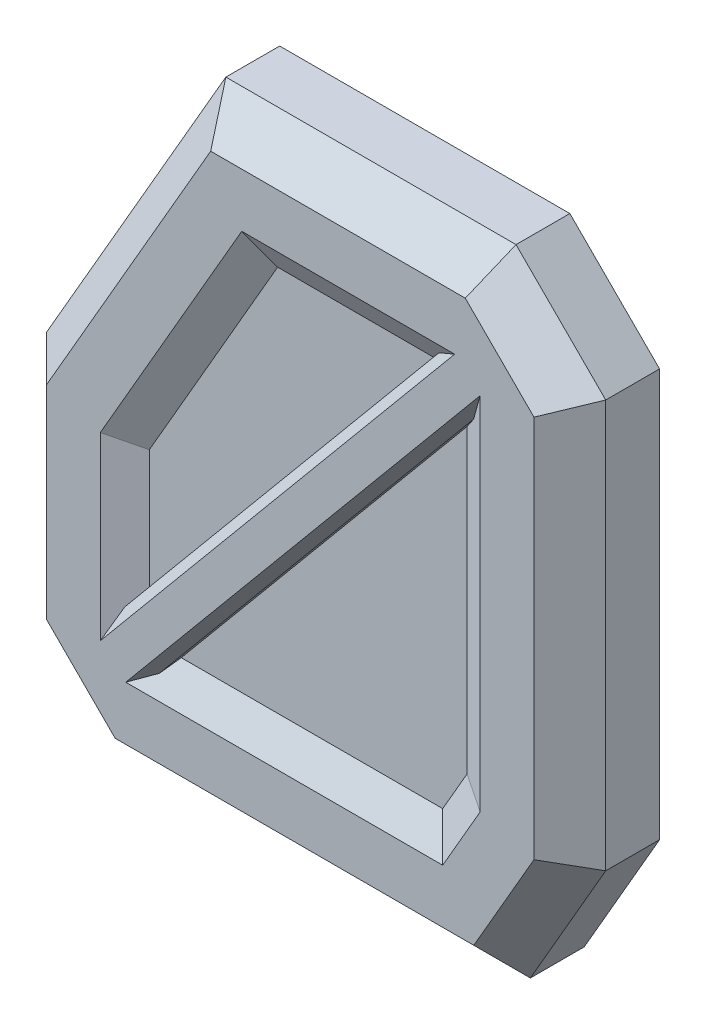
SolidWorks part; units mm, degrees
ref_plane "Plan de face" through (0, 0, 0) normal (0, 0, 1) x (1, 0, 0)
ref_plane "Plan de dessus" through (0, 0, 0) normal (0, 1, 0) x (1, 0, 0)
ref_plane "Plan de droite" through (0, 0, 0) normal (1, 0, 0) x (0, 0, -1)
sketch "Esquisse1" plane through (0, 0, 0) normal (0, 0, 1) x (1, 0, 0)
  line L0 (0, 0) -> (219.726, 0)
  line L1 (219.726, 0) -> (269.726, 50)
  line L2 (269.726, 50) -> (269.726, 176.7949)
  line L3 (269.726, 176.7949) -> (169.726, 350)
  line L4 (169.726, 350) -> (8, 350)
  line L5 (8, 350) -> (-42, 300)
  line L6 (-42, 300) -> (-42, 72.7461)
  line L7 (-42, 72.7461) -> (0, 0)
  line L8 (269.726, 176.7949) -> (269.726, 350) construction
  line L9 (269.726, 350) -> (169.726, 350) construction
  line L10 (8, 350) -> (-42, 350) construction
  line L11 (-42, 350) -> (-42, 300) construction
  line L12 (-42, 72.7461) -> (-42, 0) construction
  line L13 (-42, 0) -> (0, 0) construction
  line L14 (269.726, 50) -> (269.726, 0) construction
  line L15 (269.726, 0) -> (219.726, 0) construction
  dimension "D1" = 350
  dimension "D2" = 311.726
  dimension "D3" = 30
  dimension "D4" = 45
  dimension "D5" = 50
  dimension "D6" = 173.2051
  dimension "D7" = 50
  dimension "D8" = 72.7461
extrude "Boss.-Extru.1" add sketch "Esquisse1" along normal blind 50
chamfer "Chanfrein1" distance 20 angle 45 8 edges at (-42, 186.3731, 50) (-17, 325, 50) (88.863, 350, 50) (219.726, 263.3975, 50) (269.726, 113.3975, 50) (244.726, 25, 50) (109.863, 0, 50) (-21, 36.3731, 50)
sketch "Esquisse2" plane through (0, 0, 50) normal (0, 0, 1) x (1, 0, 0)
  line L8 (28.7107, 300) -> (219.726, 70.7107)
  line L9 (199.0153, 50) -> (8, 279.2893)
  line L16 (28.7107, 300) -> (8, 279.2893)
  line L17 (8, 279.2893) -> (8, 86.1436)
  line L18 (8, 86.1436) -> (28.8675, 50)
  line L19 (28.8675, 50) -> (199.0153, 50)
  line L20 (199.0153, 50) -> (219.726, 70.7107)
  line L21 (219.726, 70.7107) -> (219.726, 163.3975)
  line L22 (219.726, 163.3975) -> (140.8585, 300)
  line L23 (140.8585, 300) -> (28.7107, 300)
  line L24 (28.7107, 300) -> (8, 279.2893) construction
  line L25 (8, 279.2893) -> (8, 86.1436)
  line L26 (8, 86.1436) -> (28.8675, 50)
  line L27 (28.8675, 50) -> (199.0153, 50)
  line L28 (199.0153, 50) -> (219.726, 70.7107) construction
  line L29 (219.726, 70.7107) -> (219.726, 163.3975)
  line L30 (219.726, 163.3975) -> (140.8585, 300)
  line L31 (140.8585, 300) -> (28.7107, 300)
  dimension "D1" = 30
extrude "Enlèv. mat.-Extru.1" cut sketch "Esquisse2" against normal blind 10
chamfer "Chanfrein2" distance 10 angle 60 6 edges at (219.726, 117.0541, 40) (180.2923, 231.6987, 40) (84.7846, 300, 40) (113.9414, 50, 40) (18.4338, 68.0718, 40) (8, 182.7165, 40) first distance on face at (219.726, 117.0541, 45) first distance on face at (180.2923, 231.6987, 45) first distance on face at (84.7846, 300, 45) first distance on face at (113.9414, 50, 45) first distance on face at (18.4338, 68.0718, 45) first distance on face at (8, 182.7165, 45)
chamfer "Chanfrein3" distance 5 angle 45 2 edges at (103.5077, 164.6447, 50) (124.2184, 185.3553, 50)
sketch "Esquisse3" plane through (0, 0, 0) normal (0, 0, -1) x (-1, 0, 0)
  line L16 (-5.7735, 10) -> (32, 75.4256)
  line L17 (32, 75.4256) -> (32, 295.8579)
  line L18 (32, 295.8579) -> (-12.1421, 340)
  line L19 (-12.1421, 340) -> (-163.9525, 340)
  line L20 (-163.9525, 340) -> (-259.726, 174.1154)
  line L21 (-259.726, 174.1154) -> (-259.726, 54.1421)
  line L22 (-259.726, 54.1421) -> (-215.5839, 10)
  line L23 (-215.5839, 10) -> (-5.7735, 10)
  line L24 (-5.7735, 10) -> (32, 75.4256)
  line L25 (32, 75.4256) -> (32, 295.8579)
  line L26 (32, 295.8579) -> (-12.1421, 340)
  line L27 (-12.1421, 340) -> (-163.9525, 340)
  line L28 (-163.9525, 340) -> (-259.726, 174.1154)
  line L29 (-259.726, 174.1154) -> (-259.726, 54.1421)
  line L30 (-259.726, 54.1421) -> (-215.5839, 10)
  line L31 (-215.5839, 10) -> (-5.7735, 10)
  dimension "D1" = 10
extrude "Enlèv. mat.-Extru.2" cut sketch "Esquisse3" against normal blind 30
mirror "Symétrie1" about plane through (269.726, 50, 50) normal (-1, 0, 0) of bodies 103
sketch "Esquisse4" plane through (0, 350, 0) normal (0, 1, 0) x (1, 0, 0)
  line L1 (269.726, 0) -> (-42, 0)
  line L2 (269.726, 0) -> (269.726, -51.932)
  line L3 (269.726, -51.932) -> (-42, -51.932)
  line L4 (-42, 0) -> (-42, -51.932)
extrude "Enlèv. mat.-Extru.3" cut sketch "Esquisse4" against normal through all
